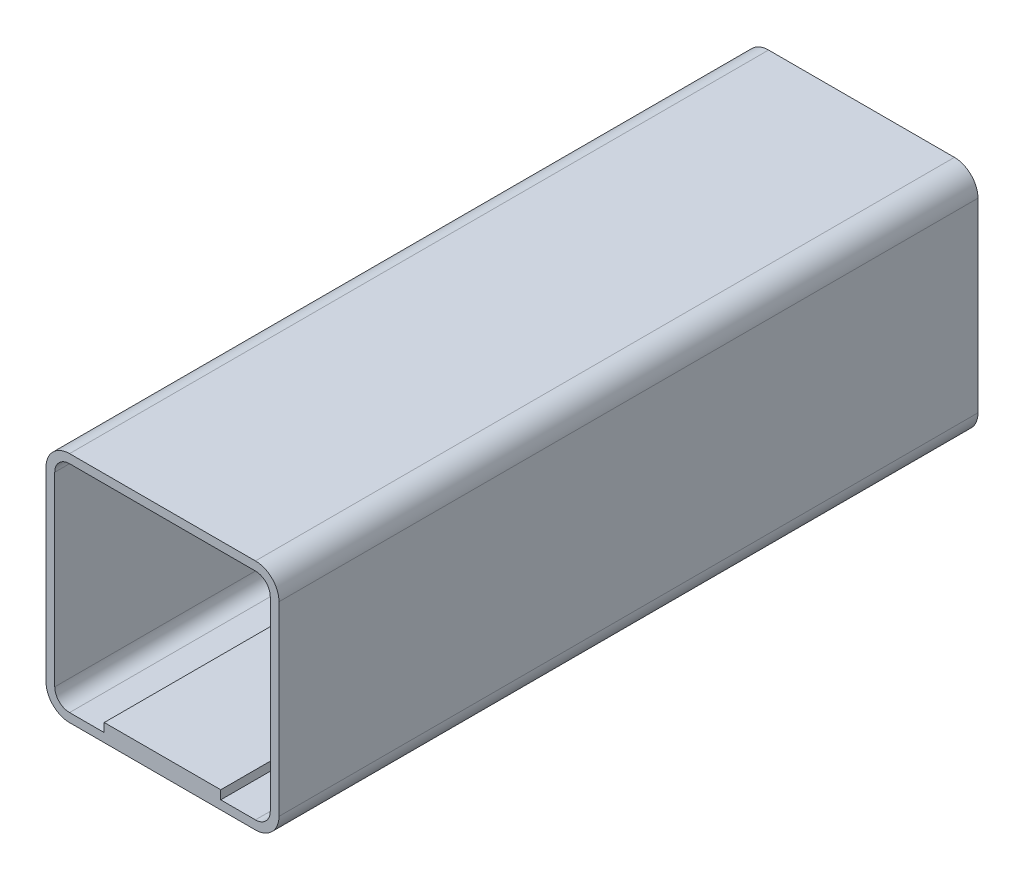
SolidWorks part; units mm, degrees
material "Polyurethane Foam Rigid"
ref_plane "Front Plane" through (0, 0, 0) normal (0, 0, 1) x (1, 0, 0)
ref_plane "Top Plane" through (0, 0, 0) normal (0, 1, 0) x (1, 0, 0)
ref_plane "Right Plane" through (0, 0, 0) normal (1, 0, 0) x (0, 0, -1)
sketch "Sketch1" plane through (0, 0, 0) normal (0, 0, 1) x (1, 0, 0)
  line L0 (-59.737, 59.737) -> (59.737, -59.737) construction
  line L1 (-50.6524, 63.5) -> (50.6524, 63.5)
  line L2 (-63.5, 50.6524) -> (-63.5, -50.6524)
  line L3 (-50.6524, -63.5) -> (50.6524, -63.5)
  line L4 (63.5, 50.6524) -> (63.5, -50.6524)
  arc A0 (63.5, 50.6524) -> (50.6524, 63.5) centre (50.6524, 50.6524) ccw
  arc A1 (50.6524, -63.5) -> (63.5, -50.6524) centre (50.6524, -50.6524) ccw
  arc A2 (-50.6524, -63.5) -> (-63.5, -50.6524) centre (-50.6524, -50.6524) cw
  arc A3 (-63.5, 50.6524) -> (-50.6524, 63.5) centre (-50.6524, 50.6524) cw
  point P0 (0, 0)
  point P1 (0, 0)
  point P18 (59.737, -59.737)
  dimension "D2" = 12.8476
  dimension "D3" = 12.8476
  dimension "D1" = 127
  dimension "D4" = 127
extrude "Boss-Extrude1" add sketch "Sketch1" against normal blind 381 contours L1 A0 L4 A1 L3 A2 L2 A3
shell "Shell1" thickness 4.7625 removed face at (0, 0, -381) removed face at (0, 0, 0)
sketch "Sketch3" plane through (0, 0, 0) normal (0, 0, 1) x (1, 0, 0)
  line L0 (-31.75, -58.7375) -> (31.75, -58.7375)
  line L1 (-50.6524, -58.7375) -> (50.6524, -58.7375) construction
  line L2 (0, -58.7375) -> (0, 0) construction
  line L3 (-31.75, -58.7375) -> (-31.75, -53.975)
  line L4 (-31.75, -53.975) -> (31.75, -53.975)
  line L5 (31.75, -53.975) -> (31.75, -58.7375)
  point P5 (0, -58.7375)
  dimension "D1" = 63.5
  dimension "D2" = 4.7625
extrude "Boss-Extrude2" add sketch "Sketch3" against normal up to surface (381 mm away) up to face at (0, 0, -381)
equation "\"span\" = 48"
equation "\"wing_chord\"= 9"
equation "\"fuse_len\"= 15"
equation "\"fuse_height\"= 5"
equation "\"fuse_wid\"= 5"
equation "\"D1@Boss-Extrude1\"= \"fuse_len\""
equation "\"D1@Sketch1\"= \"fuse_height\""
equation "\"D4@Sketch1\"= \"fuse_wid\""
equation "\"D1@Sketch3\"=\"fuse_wid\"/2"
equation "\"D2@Sketch3\"=3/16"
equation "\"foam_t\"= 0.1875"
equation "\"fuse_inner_arc_length\"= 0.5"
equation "\"fuse_inner_r\"= \"fuse_inner_arc_length\" * 4 / (2*pi)"
equation "\"fuse_outer_r\"= \"fuse_inner_r\" + \"foam_t\""
equation "\"main_spar_len\"= 36"
equation "\"x_fuse_to_wing\"= 3"
equation "\"x_cg_from_le\"= 2.25"
equation "\"boom_len\"= 36"
equation "\"wing_angle\"= 1.5"
equation "\"boom_d\"= 0.75"
equation "\"wing_spar_d\"= 0.5"
equation "\"wing_spar_l\"= 48"
equation "\"wing_spar_spacing\"= 1.35"
equation "\"wing_mount_l\" = 2.5"
equation "\"wing_mount_bolt_spacing\"= \"wing_mount_l\" + 0.5"
equation "\"boom_mount_l\"= 1"
equation "\"vstab_span\"= 6.5"
equation "\"hstab_span\"= 15.25"
equation "\"tail_chord\"= 5"
equation "\"D2@Sketch1\"= \"fuse_outer_r\""
equation "\"D3@Sketch1\"= \"fuse_outer_r\""
equation "\"fuse_inner_h\"= \"fuse_height\" - 2*\"foam_t\""
equation "\"fuse_inner_w\"= \"fuse_wid\" - 2*\"fuse_outer_r\""
